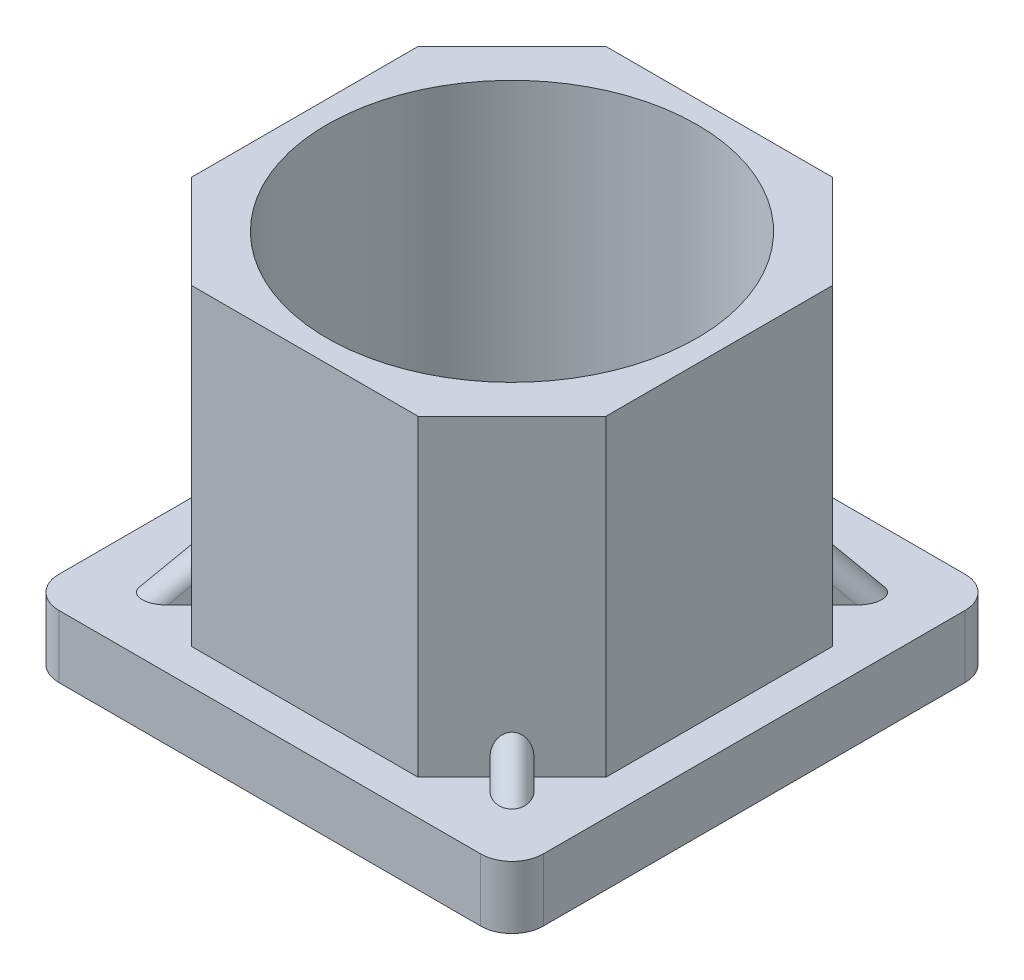
SolidWorks part; units mm, degrees
ref_plane "Plan de face" through (0, 0, 0) normal (0, 0, 1) x (1, 0, 0)
ref_plane "Plan de dessus" through (0, 0, 0) normal (0, 1, 0) x (1, 0, 0)
ref_plane "Plan de droite" through (0, 0, 0) normal (1, 0, 0) x (0, 0, -1)
sketch "Esquisse1" plane through (0, 0, 0) normal (0, 1, 0) x (1, 0, 0)
  line L0 (0, 0) -> (-30.99, 0) construction
  line L1 (-26.99, -30.99) -> (26.99, -30.99)
  line L2 (-30.99, -26.99) -> (-30.99, 26.99)
  line L3 (-26.99, 30.99) -> (26.99, 30.99)
  line L4 (30.99, -26.99) -> (30.99, 26.99)
  line L5 (0, 0) -> (30.99, 0) construction
  line L6 (0, 0) -> (0, 30.99) construction
  line L7 (0, 0) -> (0, -30.99) construction
  arc A0 (-26.99, -30.99) -> (-30.99, -26.99) centre (-26.99, -26.99) cw
  arc A1 (26.99, -30.99) -> (30.99, -26.99) centre (26.99, -26.99) ccw
  arc A2 (26.99, 30.99) -> (30.99, 26.99) centre (26.99, 26.99) cw
  arc A3 (-30.99, 26.99) -> (-26.99, 30.99) centre (-26.99, 26.99) cw
  point P7 (-29.8184, -29.8184)
  point P12 (30.99, 30.99)
  point P15 (-30.99, 30.99)
  dimension "D3" = 4
  dimension "D1" = 61.98
  dimension "D2" = 61.98
extrude "Boss.-Extru.1" add sketch "Esquisse1" along normal blind 8
sketch "Esquisse4" plane through (0, 8, 0) normal (0, 1, 0) x (1, 0, 0)
  line L0 (-26.5, 14.4792) -> (-14.4792, 26.5)
  line L1 (-14.4792, -26.5) -> (14.4792, -26.5)
  line L2 (-26.5, -14.4792) -> (-26.5, 14.4792)
  line L3 (-14.4792, 26.5) -> (14.4792, 26.5)
  line L4 (26.5, -14.4792) -> (26.5, 14.4792)
  line L5 (-26.5, 0) -> (0, 0) construction
  line L6 (0, 0) -> (26.5, 0) construction
  line L7 (14.4792, 26.5) -> (26.5, 14.4792)
  line L8 (26.5, -14.4792) -> (14.4792, -26.5)
  line L9 (-14.4792, -26.5) -> (-26.5, -14.4792)
  line L10 (-26.5, 26.5) -> (-14.4792, 26.5) construction
  line L11 (-26.5, 26.5) -> (-26.5, 14.4792) construction
  point P0 (0, 0)
  dimension "D1" = 53
  dimension "D2" = 53
  dimension "D3" = 90
  dimension "D4" = 90
  dimension "D5" = 90
  dimension "D6" = 17
extrude "Boss.-Extru.2" add sketch "Esquisse4" along normal blind 40
sketch "Esquisse5" plane through (0, 48, 0) normal (0, 1, 0) x (1, 0, 0)
  circle A0 centre (0, 0) radius 23.67
  dimension "D1" = 47.34
extrude "Enlèv. mat.-Extru.1" cut sketch "Esquisse5" against normal through all both and the other way through all
chamfer "Chanfrein1" distance 1.75 1 edges at (0, 0, 23.67)
ref_plane "Plan4" through (0, 0, 0) normal (0.7071, 0, -0.7071) x (-0.7071, 0, -0.7071)
sketch "Esquisse10" plane through (0, 0, 0) normal (0.7071, 0, -0.7071) x (-0.7071, 0, -0.7071)
  line L0 (-35.9697, 6) -> (-28.9697, 13)
  line L1 (-28.9697, 13) -> (-28.9697, 6)
  line L2 (-28.9697, 6) -> (-35.9697, 6)
  line L3 (28.9767, 15) -> (35.9767, 8)
  line L4 (28.9767, 48) -> (28.9767, 8) construction
  line L5 (2.8284, 8) -> (40.9981, 8) construction
  line L6 (35.9767, 8) -> (28.9767, 8)
  line L7 (28.9767, 8) -> (28.9767, 15)
  line L8 (0, 0) -> (-28.9697, 0) construction
  line L9 (-40.9981, 0) -> (-2.8284, 0) construction
  line L10 (-28.9697, 0) -> (-28.9697, 6) construction
  line L11 (0, 0) -> (28.9767, 0) construction
  line L12 (28.9767, 0) -> (28.9767, 8) construction
  dimension "D1" = 7
  dimension "D2" = 7
  dimension "D3" = 7
  dimension "D4" = 7
  dimension "D5" = 28.9697
  dimension "D6" = 6
extrude "Boss.-Extru.3" add sketch "Esquisse10" along normal mid plane 4
ref_plane "Plan5" through (0, 0, 0) normal (0.7071, 0, 0.7071) x (0.7071, 0, -0.7071)
sketch "Esquisse11" plane through (0, 0, 0) normal (0.7071, 0, 0.7071) x (0.7071, 0, -0.7071)
  line L0 (-35.975, 6) -> (-28.975, 13)
  line L1 (-28.975, 13) -> (-28.975, 6)
  line L2 (-28.975, 6) -> (-35.975, 6)
  line L3 (0, 0) -> (-28.975, 0) construction
  line L4 (-28.975, 0) -> (-28.975, 6) construction
  line L5 (35.975, 6) -> (28.975, 13)
  line L6 (28.975, 13) -> (28.975, 6)
  line L7 (28.975, 6) -> (35.975, 6)
  line L8 (0, 0) -> (28.975, 0) construction
  line L9 (28.975, 0) -> (28.975, 6) construction
  dimension "D1" = 6
  dimension "D2" = 7
  dimension "D3" = 7
  dimension "D4" = 28.975
  dimension "D5" = 7
  dimension "D6" = 7
  dimension "D7" = 28.975
  dimension "D8" = 6
extrude "Boss.-Extru.4" add sketch "Esquisse11" along normal mid plane 4
ref_plane "Plan6" through (7.4164, -10.4883, 7.4164) normal (0.5, -0.7071, 0.5) x (-0.866, -0.4082, 0.2887)
sketch "Esquisse12" plane through (7.4164, -10.4883, 7.4164) normal (0.5, -0.7071, 0.5) x (-0.866, -0.4082, 0.2887)
  line L0 (-15.9794, -22.5982) -> (0, 0) construction
  line L1 (-16.7287, -20.1938) -> (-18.7671, -23.0765) construction
  line L3 (-15.5011, -25.3859) -> (-13.4627, -22.5032) construction
  line L4 (-15.5011, -25.3859) -> (-18.7671, -23.0765) construction
  line L5 (-17.6124, -21.4435) -> (-15.9794, -22.5982) construction
  line L10 (-14.3464, -23.7529) -> (-15.5011, -25.3859)
  line L11 (-15.5011, -25.3859) -> (-18.7671, -23.0765)
  line L12 (-17.6124, -21.4435) -> (-18.7671, -23.0765)
  arc A1 (-17.6124, -21.4435) -> (-14.3464, -23.7529) centre (-15.9794, -22.5982) ccw
ref_plane "Plan8" through (7.4164, -10.4883, -7.4164) normal (0.5, -0.7071, -0.5) x (-0.866, -0.4082, -0.2887)
sketch "Esquisse13" plane through (7.4164, -10.4883, -7.4164) normal (0.5, -0.7071, -0.5) x (-0.866, -0.4082, -0.2887)
  line L0 (0, 0) -> (-15.9812, 22.6008) construction
  line L1 (-18.7692, 23.0796) -> (-16.7287, 20.1938) construction
  line L2 (-13.4627, 22.5032) -> (-15.5032, 25.389) construction
  line L3 (-18.7692, 23.0796) -> (-15.5032, 25.389) construction
  line L4 (-17.586, 21.4062) -> (-18.7692, 23.0796)
  line L5 (-18.7692, 23.0796) -> (-15.5032, 25.389)
  line L6 (-15.5032, 25.389) -> (-14.32, 23.7156)
  arc A0 (-17.586, 21.4062) -> (-14.32, 23.7156) centre (-15.9812, 22.6008) cw
extrude "Enlèv. mat.-Extru.4" cut sketch "Esquisse13" against normal up to surface and the other way up to surface contours A0 | A0 region at (20.9355, 10.1837, -23.1319) region at (23.1319, 10.1837, -20.9355) up to face at (20.4896, 19.2496, -20.4896) other way up to face at (0, 8, 0)
ref_plane "Plan9" through (-7.4164, -10.4883, -7.4164) normal (-0.5, -0.7071, -0.5) x (-0.866, 0.4082, 0.2887)
sketch "Esquisse15" plane through (-7.4164, -10.4883, -7.4164) normal (-0.5, -0.7071, -0.5) x (-0.866, 0.4082, 0.2887)
  line L0 (0, 0) -> (15.7629, 22.2921) construction
  line L1 (16.3204, 26.5446) -> (13.4627, 22.5032) construction
  line L2 (19.5864, 24.2352) -> (16.7287, 20.1938) construction
  line L3 (14.1874, 23.5281) -> (16.3204, 26.5446)
  line L4 (16.3204, 26.5446) -> (19.5864, 24.2352) construction
  line L5 (16.3204, 26.5446) -> (19.5864, 24.2352)
  line L6 (19.5864, 24.2352) -> (17.4534, 21.2187)
  arc A0 (14.1874, 23.5281) -> (17.4534, 21.2187) centre (15.7629, 22.2921) cw
  dimension "D2" = 2.0025
  dimension "D1" = 27.3021
extrude "Enlèv. mat.-Extru.6" cut sketch "Esquisse15" against normal up to surface and the other way up to surface up to face at (-20.4896, 19.75, -20.4896) other way up to face at (-0.1996, 8, -0.0369)
ref_plane "Plan10" through (-7.4164, -10.4883, 7.4164) normal (-0.5, -0.7071, 0.5) x (-0.866, 0.4082, -0.2887)
sketch "Esquisse16" plane through (-7.4164, -10.4883, 7.4164) normal (-0.5, -0.7071, 0.5) x (-0.866, 0.4082, -0.2887)
  line L0 (0, 0) -> (15.9815, -22.6013) construction
  line L1 (18.7692, -23.0796) -> (16.7287, -20.1938) construction
  line L4 (18.7692, -23.0796) -> (15.5032, -25.389) construction
  line L9 (13.4627, -22.5032) -> (15.5032, -25.389) construction
  line L10 (18.7692, -23.0796) -> (16.7287, -20.1938) construction
  line L11 (17.6145, -21.4466) -> (15.9815, -22.6013) construction
  line L12 (17.6145, -21.4466) -> (18.7692, -23.0796)
  line L13 (18.7692, -23.0796) -> (15.5032, -25.389)
  line L14 (15.5032, -25.389) -> (14.3485, -23.756)
  arc A1 (17.6145, -21.4466) -> (14.3485, -23.756) centre (15.9815, -22.6013) cw
extrude "Enlèv. mat.-Extru.7" cut sketch "Esquisse16" against normal up to surface and the other way up to surface contours L12 A1 L13 | L13 A1 L14 region at (-20.9351, 10.1833, 23.1317) region at (-23.1317, 10.1833, 20.9351) up to face at (-20.4896, 19.2496, 20.4896) other way up to face at (0.029, 8, 0.1916)
extrude "Enlèv. mat.-Extru.8" cut sketch "Esquisse12" against normal up to surface and the other way up to surface contours A1 L12 L11 | A1 L11 L10 region at (23.1299, 10.1806, 20.9332) region at (20.9332, 10.1806, 23.1299) up to face at (20.4896, 19.2483, 20.4896) other way up to face at (0.1123, 8, 0.1083)
